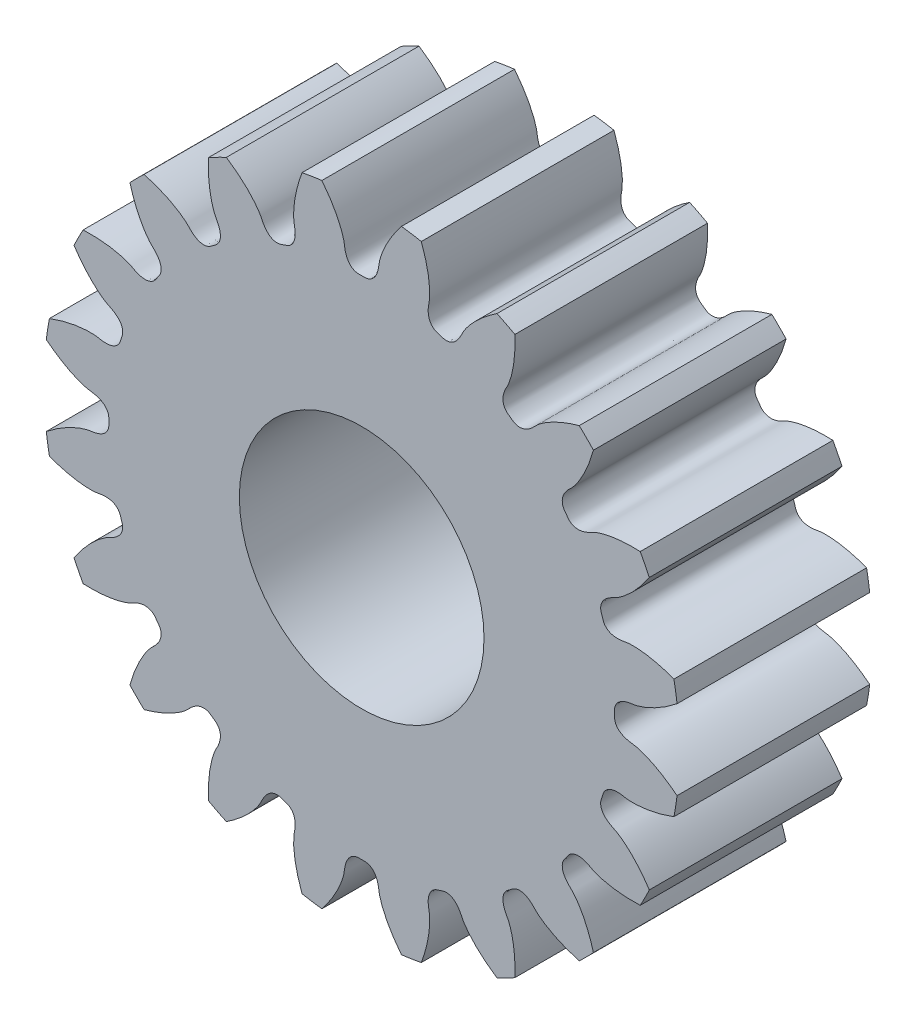
SolidWorks part; units mm, degrees
ref_plane "Front Plane" through (0, 0, 0) normal (0, 0, 1) x (1, 0, 0)
ref_plane "Top Plane" through (0, 0, 0) normal (0, 1, 0) x (1, 0, 0)
ref_plane "Right Plane" through (0, 0, 0) normal (1, 0, 0) x (0, 0, -1)
ref_axis "Axis1" through (0, 0, 55) along (0, 0, -1)
sketch "SketchRevolveSpurAssembly01Pinion" plane through (0, 0, 0) normal (1, 0, 0) x (0, 0, -1)
  line L0 (0, 0) -> (1, 0) construction
  line L1 (-5, 0) -> (-5, 16.5)
  line L2 (-5, 16.5) -> (5, 16.5)
  line L3 (5, 16.5) -> (5, 0)
  line L4 (5, 0) -> (-5, 0)
  dimension "Side1" = 5
  dimension "OutsideRadius" = 16.5
  dimension "Side2" = 5
revolve "SpurAssembly01Pinion" add sketch "SketchRevolveSpurAssembly01Pinion" angle 360 about L0
sketch "SketchToothSpurAssembly01Pinion" plane through (0, 0, 0) normal (0, 0, 1) x (1, 0, 0)
  arc A0 (16.4388, 2.1204) -> (16.4388, -2.1204) centre (0, 0) cw
  spline S0 degree 3 poles (16.4388, -2.1204) (16.3062, -2.0126) (16.1079, -1.8609) (15.8417, -1.6767) (15.6549, -1.5557) (15.4759, -1.4476) (15.3054, -1.3516) (15.1441, -1.2672) (14.9923, -1.1937) (14.8506, -1.1305) (14.7196, -1.0767) (14.5996, -1.0318) (14.491, -0.9949) (14.3942, -0.9653) (14.3096, -0.9423) (14.2375, -0.925) (14.178, -0.9126) (14.0492, -0.8903) (13.9123, -0.8782) (13.7697, -0.8427) (13.6956, -0.8206) (13.6244, -0.795) (13.5557, -0.7654) (13.4893, -0.7311) (13.4248, -0.6913) (13.3623, -0.6446) (13.3021, -0.5892) (13.2452, -0.523) (13.1943, -0.4439) (13.1533, -0.3509) (13.1303, -0.2534) (13.1208, -0.135) (13.1277, 0) (13.1208, 0.135) (13.1303, 0.2534) (13.1533, 0.3509) (13.1943, 0.4439) (13.2452, 0.523) (13.3021, 0.5892) (13.3623, 0.6446) (13.4248, 0.6913) (13.4893, 0.7311) (13.5557, 0.7654) (13.6244, 0.795) (13.6956, 0.8206) (13.7697, 0.8427) (13.9123, 0.8782) (14.0492, 0.8903) (14.178, 0.9126) (14.2375, 0.925) (14.3096, 0.9423) (14.3942, 0.9653) (14.491, 0.9949) (14.5996, 1.0318) (14.7196, 1.0767) (14.8506, 1.1305) (14.9923, 1.1937) (15.1441, 1.2672) (15.3054, 1.3516) (15.4759, 1.4476) (15.6549, 1.5557) (15.8417, 1.6767) (16.1079, 1.8609) (16.3062, 2.0126) (16.4388, 2.1204) knots 0 0 0 0 0.061423 0.08971 0.11638 0.141434 0.164872 0.186693 0.206898 0.225486 0.242459 0.257814 0.271554 0.283677 0.294183 0.303073 0.310347 0.316004 0.350077 0.359568 0.368803 0.377844 0.386769 0.395676 0.404689 0.413963 0.423683 0.434051 0.445256 0.457401 0.47042 0.481067 0.5 0.518933 0.52958 0.542599 0.554744 0.565949 0.576317 0.586037 0.595311 0.604324 0.613231 0.622156 0.631197 0.640432 0.649923 0.683996 0.689653 0.696927 0.705817 0.716323 0.728446 0.742186 0.757541 0.774514 0.793102 0.813307 0.835128 0.858566 0.88362 0.91029 0.938577 1 1 1 1
extrude "ToothExtrudeCutSpurAssembly01Pinion" cut sketch "SketchToothSpurAssembly01Pinion" against normal blind 5 and the other way blind 5
pattern_circular "PatternSpurAssembly01Pinion" count 20 every 18 about axis through (0, 0, 55) along (0, 0, -1) of "ToothExtrudeCutSpurAssembly01Pinion"
sketch "BoreRevolveSketch" plane through (0, 0, 0) normal (1, 0, 0) x (0, 0, -1)
  line L0 (0, 0) -> (1, 0) construction
  line L1 (-5, 0) -> (5, 0)
  line L2 (5, 0) -> (5, 6.35)
  line L3 (5, 6.35) -> (-5, 6.35)
  line L4 (-5, 6.35) -> (-5, 0)
  dimension "BoreSide1" = 5
  dimension "TaperSide1" = 6.35
  dimension "BoreSide2" = 5
  dimension "TaperSide2" = 6.35
revolve "BoreRevolveCut" cut sketch "BoreRevolveSketch" angle 360 about L0
sketch "AuxiliarySketchSpurAssembly01Pinion" plane through (0, 0, 0) normal (0, 0, 1) x (1, 0, 0)
  circle A0 centre (0, 0) radius 15 construction
  circle A1 centre (0, 0) radius 14.0954 construction
  circle A2 centre (0, 0) radius 14.1048 construction
  circle A3 centre (0, 0) radius 16.5 construction
  circle A4 centre (0, 0) radius 13.125 construction
  point P7 (0, 0)
  point P8 (0, 0)
  dimension "PitchDiameter" = 30
  dimension "BaseDiameter" = 28.1908
  dimension "FormDiameter" = 28.2095
  dimension "MajorDiameter" = 33
  dimension "MinorDiameter" = 26.25
